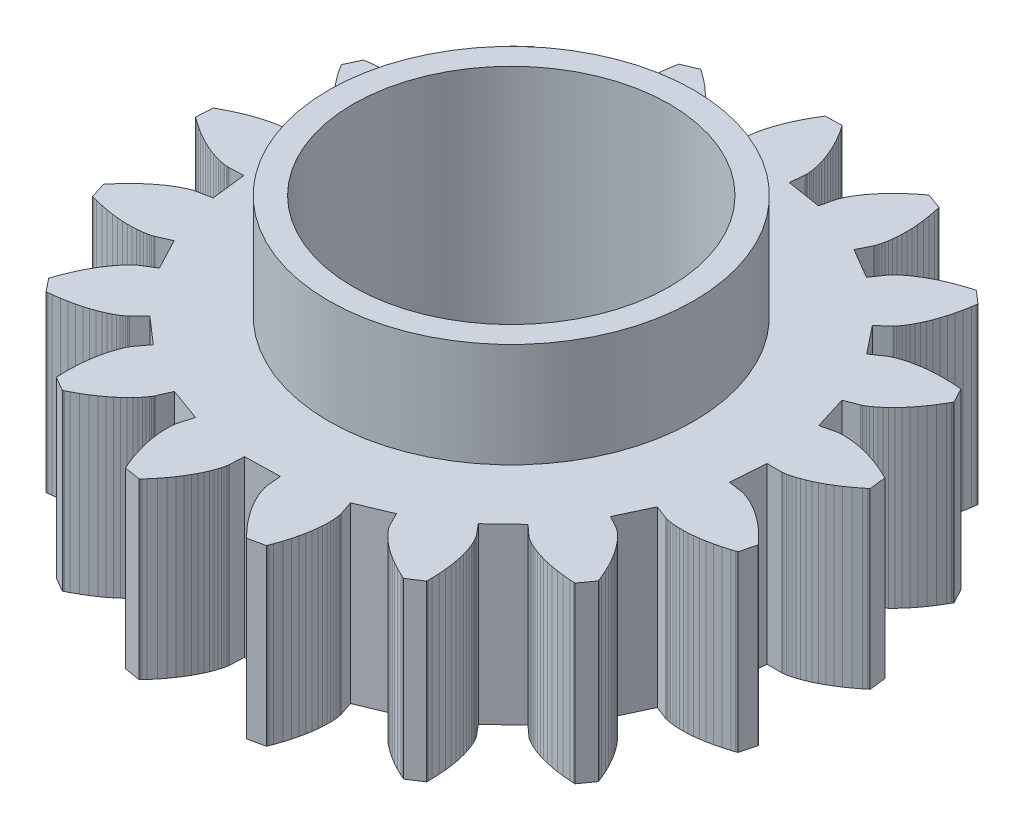
SolidWorks part; units mm, degrees
ref_plane "Front Plane" through (0, 0, 0) normal (0, 0, 1) x (1, 0, 0)
ref_plane "Top Plane" through (0, 0, 0) normal (0, 1, 0) x (1, 0, 0)
ref_plane "Right Plane" through (0, 0, 0) normal (1, 0, 0) x (0, 0, -1)
sketch "Sketch1" plane through (0, 0, 0) normal (0, 1, 0) x (1, 0, 0)
  line L0 (7.35, 0) -> (7.7663, 0)
  line L1 (7.7663, 0) -> (7.7784, 0.0005)
  line L2 (7.7784, 0.0005) -> (7.8035, 0.0026)
  line L3 (7.8035, 0.0026) -> (7.8416, 0.0072)
  line L4 (7.8416, 0.0072) -> (7.8923, 0.0155)
  line L5 (7.8923, 0.0155) -> (7.9555, 0.0285)
  line L6 (7.9555, 0.0285) -> (8.0307, 0.0472)
  line L7 (8.0307, 0.0472) -> (8.1178, 0.0727)
  line L8 (8.1178, 0.0727) -> (8.2161, 0.1059)
  line L9 (8.2161, 0.1059) -> (8.3252, 0.1478)
  line L10 (8.3252, 0.1478) -> (8.4445, 0.1994)
  line L11 (8.4445, 0.1994) -> (8.5734, 0.2615)
  line L12 (8.5734, 0.2615) -> (8.7111, 0.335)
  line L13 (8.7111, 0.335) -> (8.8571, 0.4207)
  line L14 (8.8571, 0.4207) -> (9.0104, 0.5194)
  line L15 (9.0104, 0.5194) -> (9.1702, 0.6319)
  line L16 (9.1702, 0.6319) -> (9.3357, 0.7588)
  line L17 (9.3357, 0.7588) -> (9.4203, 0.8278)
  line L18 (9.4203, 0.8278) -> (9.4416, 0.8457)
  line L19 (9.4416, 0.8457) -> (9.4523, 0.8547)
  line L20 (9.4523, 0.8547) -> (9.4576, 0.8593)
  line L21 (9.4576, 0.8593) -> (9.4603, 0.8615)
  line L22 (9.4603, 0.8615) -> (9.4606, 0.8618)
  line L23 (9.4606, 0.8618) -> (9.4608, 0.8621)
  line L24 (9.4608, 0.8621) -> (9.4055, 1.3364)
  line L25 (9.4055, 1.3364) -> (9.4053, 1.3367)
  line L26 (9.4053, 1.3367) -> (9.4049, 1.3369)
  line L27 (9.4049, 1.3369) -> (9.4018, 1.3385)
  line L28 (9.4018, 1.3385) -> (9.3955, 1.3416)
  line L29 (9.3955, 1.3416) -> (9.3831, 1.348)
  line L30 (9.3831, 1.348) -> (9.3582, 1.3605)
  line L31 (9.3582, 1.3605) -> (9.26, 1.4082)
  line L32 (9.26, 1.4082) -> (9.0698, 1.4937)
  line L33 (9.0698, 1.4937) -> (8.8884, 1.5664)
  line L34 (8.8884, 1.5664) -> (8.7165, 1.6272)
  line L35 (8.7165, 1.6272) -> (8.5547, 1.677)
  line L36 (8.5547, 1.677) -> (8.4038, 1.7169)
  line L37 (8.4038, 1.7169) -> (8.2641, 1.7477)
  line L38 (8.2641, 1.7477) -> (8.1361, 1.7704)
  line L39 (8.1361, 1.7704) -> (8.0203, 1.7861)
  line L40 (8.0203, 1.7861) -> (7.917, 1.7959)
  line L41 (7.917, 1.7959) -> (7.8264, 1.8007)
  line L42 (7.8264, 1.8007) -> (7.7488, 1.8016)
  line L43 (7.7488, 1.8016) -> (7.6844, 1.7997)
  line L44 (7.6844, 1.7997) -> (7.6331, 1.7961)
  line L45 (7.6331, 1.7961) -> (7.595, 1.7919)
  line L46 (7.595, 1.7919) -> (7.5701, 1.7881)
  line L47 (7.5701, 1.7881) -> (7.5582, 1.7858)
  line L48 (7.5582, 1.7858) -> (7.1531, 1.6901)
  line L49 (7.1531, 1.6901) -> (6.8537, 2.6551)
  line L50 (6.8537, 2.6551) -> (7.2419, 2.8055)
  line L51 (7.2419, 2.8055) -> (7.253, 2.8104)
  line L52 (7.253, 2.8104) -> (7.2757, 2.8213)
  line L53 (7.2757, 2.8213) -> (7.3094, 2.8394)
  line L54 (7.3094, 2.8394) -> (7.3537, 2.8655)
  line L55 (7.3537, 2.8655) -> (7.408, 2.9004)
  line L56 (7.408, 2.9004) -> (7.4714, 2.9451)
  line L57 (7.4714, 2.9451) -> (7.5433, 3.0003)
  line L58 (7.5433, 3.0003) -> (7.623, 3.0668)
  line L59 (7.623, 3.0668) -> (7.7096, 3.1453)
  line L60 (7.7096, 3.1453) -> (7.8022, 3.2364)
  line L61 (7.8022, 3.2364) -> (7.9, 3.3409)
  line L62 (7.9, 3.3409) -> (8.0019, 3.4592)
  line L63 (8.0019, 3.4592) -> (8.107, 3.5918)
  line L64 (8.107, 3.5918) -> (8.2143, 3.7393)
  line L65 (8.2143, 3.7393) -> (8.3227, 3.9019)
  line L66 (8.3227, 3.9019) -> (8.4312, 4.08)
  line L67 (8.4312, 4.08) -> (8.4851, 4.1749)
  line L68 (8.4851, 4.1749) -> (8.4985, 4.1993)
  line L69 (8.4985, 4.1993) -> (8.5052, 4.2116)
  line L70 (8.5052, 4.2116) -> (8.5085, 4.2177)
  line L71 (8.5085, 4.2177) -> (8.5102, 4.2208)
  line L72 (8.5102, 4.2208) -> (8.5104, 4.2212)
  line L73 (8.5104, 4.2212) -> (8.5105, 4.2215)
  line L74 (8.5105, 4.2215) -> (8.2876, 4.6439)
  line L75 (8.2876, 4.6439) -> (8.2873, 4.644)
  line L76 (8.2873, 4.644) -> (8.2869, 4.644)
  line L77 (8.2869, 4.644) -> (8.2834, 4.6444)
  line L78 (8.2834, 4.6444) -> (8.2764, 4.6451)
  line L79 (8.2764, 4.6451) -> (8.2625, 4.6465)
  line L80 (8.2625, 4.6465) -> (8.2348, 4.6492)
  line L81 (8.2348, 4.6492) -> (8.126, 4.6582)
  line L82 (8.126, 4.6582) -> (7.9178, 4.6692)
  line L83 (7.9178, 4.6692) -> (7.7223, 4.6714)
  line L84 (7.7223, 4.6714) -> (7.5401, 4.6661)
  line L85 (7.5401, 4.6661) -> (7.3712, 4.6541)
  line L86 (7.3712, 4.6541) -> (7.2161, 4.6367)
  line L87 (7.2161, 4.6367) -> (7.0747, 4.615)
  line L88 (7.0747, 4.615) -> (6.9471, 4.59)
  line L89 (6.9471, 4.59) -> (6.8335, 4.5628)
  line L90 (6.8335, 4.5628) -> (6.7336, 4.5345)
  line L91 (6.7336, 4.5345) -> (6.6474, 4.5063)
  line L92 (6.6474, 4.5063) -> (6.5748, 4.4791)
  line L93 (6.5748, 4.4791) -> (6.5153, 4.4541)
  line L94 (6.5153, 4.4541) -> (6.4688, 4.4322)
  line L95 (6.4688, 4.4322) -> (6.4349, 4.4145)
  line L96 (6.4349, 4.4145) -> (6.413, 4.402)
  line L97 (6.413, 4.402) -> (6.4027, 4.3955)
  line L98 (6.4027, 4.3955) -> (6.0595, 4.1599)
  line L99 (6.0595, 4.1599) -> (5.4317, 4.9517)
  line L100 (5.4317, 4.9517) -> (5.7394, 5.2321)
  line L101 (5.7394, 5.2321) -> (5.748, 5.2407)
  line L102 (5.748, 5.2407) -> (5.7652, 5.2591)
  line L103 (5.7652, 5.2591) -> (5.7901, 5.2881)
  line L104 (5.7901, 5.2881) -> (5.822, 5.3284)
  line L105 (5.822, 5.3284) -> (5.86, 5.3806)
  line L106 (5.86, 5.3806) -> (5.903, 5.4452)
  line L107 (5.903, 5.4452) -> (5.9501, 5.5226)
  line L108 (5.9501, 5.5226) -> (6.0004, 5.6134)
  line L109 (6.0004, 5.6134) -> (6.0528, 5.7179)
  line L110 (6.0528, 5.7179) -> (6.1062, 5.8364)
  line L111 (6.1062, 5.8364) -> (6.1596, 5.9691)
  line L112 (6.1596, 5.9691) -> (6.2119, 6.1162)
  line L113 (6.2119, 6.1162) -> (6.262, 6.2779)
  line L114 (6.262, 6.2779) -> (6.3088, 6.4541)
  line L115 (6.3088, 6.4541) -> (6.3512, 6.6449)
  line L116 (6.3512, 6.6449) -> (6.388, 6.8502)
  line L117 (6.388, 6.8502) -> (6.4039, 6.9582)
  line L118 (6.4039, 6.9582) -> (6.4077, 6.9857)
  line L119 (6.4077, 6.9857) -> (6.4095, 6.9996)
  line L120 (6.4095, 6.9996) -> (6.4104, 7.0066)
  line L121 (6.4104, 7.0066) -> (6.4108, 7.01)
  line L122 (6.4108, 7.01) -> (6.4109, 7.0105)
  line L123 (6.4109, 7.0105) -> (6.4108, 7.0108)
  line L124 (6.4108, 7.0108) -> (6.0504, 7.3241)
  line L125 (6.0504, 7.3241) -> (6.0501, 7.3241)
  line L126 (6.0501, 7.3241) -> (6.0497, 7.324)
  line L127 (6.0497, 7.324) -> (6.0463, 7.3231)
  line L128 (6.0463, 7.3231) -> (6.0395, 7.3212)
  line L129 (6.0395, 7.3212) -> (6.026, 7.3175)
  line L130 (6.026, 7.3175) -> (5.9993, 7.31)
  line L131 (5.9993, 7.31) -> (5.8945, 7.2791)
  line L132 (5.8945, 7.2791) -> (5.6964, 7.2141)
  line L133 (5.6964, 7.2141) -> (5.5133, 7.1456)
  line L134 (5.5133, 7.1456) -> (5.3453, 7.0748)
  line L135 (5.3453, 7.0748) -> (5.1922, 7.0026)
  line L136 (5.1922, 7.0026) -> (5.0538, 6.9304)
  line L137 (5.0538, 6.9304) -> (4.9298, 6.859)
  line L138 (4.9298, 6.859) -> (4.8199, 6.7896)
  line L139 (4.8199, 6.7896) -> (4.7237, 6.7232)
  line L140 (4.7237, 6.7232) -> (4.6408, 6.6608)
  line L141 (4.6408, 6.6608) -> (4.5707, 6.6033)
  line L142 (4.5707, 6.6033) -> (4.5127, 6.5517)
  line L143 (4.5127, 6.5517) -> (4.4664, 6.5069)
  line L144 (4.4664, 6.5069) -> (4.4309, 6.4697)
  line L145 (4.4309, 6.4697) -> (4.4056, 6.441)
  line L146 (4.4056, 6.441) -> (4.3898, 6.4214)
  line L147 (4.3898, 6.4214) -> (4.3825, 6.4117)
  line L148 (4.3825, 6.4117) -> (4.1476, 6.068)
  line L149 (4.1476, 6.068) -> (3.2762, 6.5794)
  line L150 (3.2762, 6.5794) -> (3.4617, 6.9521)
  line L151 (3.4617, 6.9521) -> (3.4667, 6.9632)
  line L152 (3.4667, 6.9632) -> (3.4761, 6.9866)
  line L153 (3.4761, 6.9866) -> (3.4889, 7.0227)
  line L154 (3.4889, 7.0227) -> (3.504, 7.0718)
  line L155 (3.504, 7.0718) -> (3.5206, 7.1341)
  line L156 (3.5206, 7.1341) -> (3.5373, 7.2099)
  line L157 (3.5373, 7.2099) -> (3.5533, 7.2991)
  line L158 (3.5533, 7.2991) -> (3.5674, 7.402)
  line L159 (3.5674, 7.402) -> (3.5785, 7.5183)
  line L160 (3.5785, 7.5183) -> (3.5855, 7.6481)
  line L161 (3.5855, 7.6481) -> (3.5874, 7.7911)
  line L162 (3.5874, 7.7911) -> (3.583, 7.9472)
  line L163 (3.583, 7.9472) -> (3.5713, 8.1161)
  line L164 (3.5713, 8.1161) -> (3.5513, 8.2973)
  line L165 (3.5513, 8.2973) -> (3.5219, 8.4905)
  line L166 (3.5219, 8.4905) -> (3.482, 8.6952)
  line L167 (3.482, 8.6952) -> (3.4579, 8.8017)
  line L168 (3.4579, 8.8017) -> (3.4514, 8.8287)
  line L169 (3.4514, 8.8287) -> (3.4481, 8.8423)
  line L170 (3.4481, 8.8423) -> (3.4464, 8.8491)
  line L171 (3.4464, 8.8491) -> (3.4456, 8.8525)
  line L172 (3.4456, 8.8525) -> (3.4455, 8.8529)
  line L173 (3.4455, 8.8529) -> (3.4453, 8.8532)
  line L174 (3.4453, 8.8532) -> (2.9961, 9.0152)
  line L175 (2.9961, 9.0152) -> (2.9958, 9.0151)
  line L176 (2.9958, 9.0151) -> (2.9954, 9.0148)
  line L177 (2.9954, 9.0148) -> (2.9926, 9.0127)
  line L178 (2.9926, 9.0127) -> (2.987, 9.0085)
  line L179 (2.987, 9.0085) -> (2.9757, 9.0002)
  line L180 (2.9757, 9.0002) -> (2.9535, 8.9835)
  line L181 (2.9535, 8.9835) -> (2.867, 8.9169)
  line L182 (2.867, 8.9169) -> (2.7057, 8.7847)
  line L183 (2.7057, 8.7847) -> (2.5597, 8.6547)
  line L184 (2.5597, 8.6547) -> (2.4287, 8.528)
  line L185 (2.4287, 8.528) -> (2.3119, 8.4054)
  line L186 (2.3119, 8.4054) -> (2.209, 8.288)
  line L187 (2.209, 8.288) -> (2.1191, 8.1767)
  line L188 (2.1191, 8.1767) -> (2.0417, 8.0723)
  line L189 (2.0417, 8.0723) -> (1.9761, 7.9756)
  line L190 (1.9761, 7.9756) -> (1.9213, 7.8875)
  line L191 (1.9213, 7.8875) -> (1.8766, 7.8085)
  line L192 (1.8766, 7.8085) -> (1.8412, 7.7395)
  line L193 (1.8412, 7.7395) -> (1.8142, 7.681)
  line L194 (1.8142, 7.681) -> (1.7946, 7.6335)
  line L195 (1.7946, 7.6335) -> (1.7814, 7.5975)
  line L196 (1.7814, 7.5975) -> (1.7737, 7.5735)
  line L197 (1.7737, 7.5735) -> (1.7704, 7.5618)
  line L198 (1.7704, 7.5618) -> (1.6755, 7.1565)
  line L199 (1.6755, 7.1565) -> (0.6782, 7.3186)
  line L200 (0.6782, 7.3186) -> (0.7166, 7.7332)
  line L201 (0.7166, 7.7332) -> (0.7172, 7.7453)
  line L202 (0.7172, 7.7453) -> (0.7175, 7.7705)
  line L203 (0.7175, 7.7705) -> (0.7164, 7.8088)
  line L204 (0.7164, 7.8088) -> (0.7128, 7.8601)
  line L205 (0.7128, 7.8601) -> (0.7057, 7.9241)
  line L206 (0.7057, 7.9241) -> (0.694, 8.0008)
  line L207 (0.694, 8.0008) -> (0.6766, 8.0899)
  line L208 (0.6766, 8.0899) -> (0.6526, 8.1908)
  line L209 (0.6526, 8.1908) -> (0.6209, 8.3033)
  line L210 (0.6209, 8.3033) -> (0.5806, 8.4269)
  line L211 (0.5806, 8.4269) -> (0.5307, 8.5609)
  line L212 (0.5307, 8.5609) -> (0.4702, 8.7049)
  line L213 (0.4702, 8.7049) -> (0.3983, 8.8581)
  line L214 (0.3983, 8.8581) -> (0.3142, 9.0199)
  line L215 (0.3142, 9.0199) -> (0.2169, 9.1894)
  line L216 (0.2169, 9.1894) -> (0.1058, 9.3659)
  line L217 (0.1058, 9.3659) -> (0.0449, 9.4565)
  line L218 (0.0449, 9.4565) -> (0.0291, 9.4793)
  line L219 (0.0291, 9.4793) -> (0.0211, 9.4908)
  line L220 (0.0211, 9.4908) -> (0.017, 9.4965)
  line L221 (0.017, 9.4965) -> (0.015, 9.4994)
  line L222 (0.015, 9.4994) -> (0.0148, 9.4998)
  line L223 (0.0148, 9.4998) -> (0.0145, 9.5)
  line L224 (0.0145, 9.5) -> (-0.4629, 9.4887)
  line L225 (-0.4629, 9.4887) -> (-0.4632, 9.4885)
  line L226 (-0.4632, 9.4885) -> (-0.4634, 9.4881)
  line L227 (-0.4634, 9.4881) -> (-0.4653, 9.4852)
  line L228 (-0.4653, 9.4852) -> (-0.469, 9.4792)
  line L229 (-0.469, 9.4792) -> (-0.4765, 9.4674)
  line L230 (-0.4765, 9.4674) -> (-0.4912, 9.4438)
  line L231 (-0.4912, 9.4438) -> (-0.5478, 9.3505)
  line L232 (-0.5478, 9.3505) -> (-0.6504, 9.1689)
  line L233 (-0.6504, 9.1689) -> (-0.7396, 8.995)
  line L234 (-0.7396, 8.995) -> (-0.816, 8.8294)
  line L235 (-0.816, 8.8294) -> (-0.8806, 8.673)
  line L236 (-0.8806, 8.673) -> (-0.9342, 8.5263)
  line L237 (-0.9342, 8.5263) -> (-0.9777, 8.3901)
  line L238 (-0.9777, 8.3901) -> (-1.0122, 8.2647)
  line L239 (-1.0122, 8.2647) -> (-1.0385, 8.1509)
  line L240 (-1.0385, 8.1509) -> (-1.0577, 8.0489)
  line L241 (-1.0577, 8.0489) -> (-1.0708, 7.9592)
  line L242 (-1.0708, 7.9592) -> (-1.0789, 7.882)
  line L243 (-1.0789, 7.882) -> (-1.083, 7.8176)
  line L244 (-1.083, 7.8176) -> (-1.0842, 7.7663)
  line L245 (-1.0842, 7.7663) -> (-1.0835, 7.728)
  line L246 (-1.0835, 7.728) -> (-1.082, 7.7028)
  line L247 (-1.082, 7.7028) -> (-1.0808, 7.6907)
  line L248 (-1.0808, 7.6907) -> (-1.0229, 7.2785)
  line L249 (-1.0229, 7.2785) -> (-2.0114, 7.0694)
  line L250 (-2.0114, 7.0694) -> (-2.1254, 7.4698)
  line L251 (-2.1254, 7.4698) -> (-2.1292, 7.4813)
  line L252 (-2.1292, 7.4813) -> (-2.138, 7.505)
  line L253 (-2.138, 7.505) -> (-2.1529, 7.5403)
  line L254 (-2.1529, 7.5403) -> (-2.1747, 7.5868)
  line L255 (-2.1747, 7.5868) -> (-2.2045, 7.644)
  line L256 (-2.2045, 7.644) -> (-2.2431, 7.7113)
  line L257 (-2.2431, 7.7113) -> (-2.2915, 7.788)
  line L258 (-2.2915, 7.788) -> (-2.3503, 7.8735)
  line L259 (-2.3503, 7.8735) -> (-2.4205, 7.9669)
  line L260 (-2.4205, 7.9669) -> (-2.5027, 8.0675)
  line L261 (-2.5027, 8.0675) -> (-2.5977, 8.1745)
  line L262 (-2.5977, 8.1745) -> (-2.7061, 8.2869)
  line L263 (-2.7061, 8.2869) -> (-2.8285, 8.4038)
  line L264 (-2.8285, 8.4038) -> (-2.9654, 8.5243)
  line L265 (-2.9654, 8.5243) -> (-3.1173, 8.6472)
  line L266 (-3.1173, 8.6472) -> (-3.2847, 8.7717)
  line L267 (-3.2847, 8.7717) -> (-3.3742, 8.8341)
  line L268 (-3.3742, 8.8341) -> (-3.3972, 8.8497)
  line L269 (-3.3972, 8.8497) -> (-3.4088, 8.8575)
  line L270 (-3.4088, 8.8575) -> (-3.4147, 8.8614)
  line L271 (-3.4147, 8.8614) -> (-3.4176, 8.8634)
  line L272 (-3.4176, 8.8634) -> (-3.4179, 8.8636)
  line L273 (-3.4179, 8.8636) -> (-3.4183, 8.8637)
  line L274 (-3.4183, 8.8637) -> (-3.8594, 8.6807)
  line L275 (-3.8594, 8.6807) -> (-3.8595, 8.6804)
  line L276 (-3.8595, 8.6804) -> (-3.8596, 8.68)
  line L277 (-3.8596, 8.68) -> (-3.8603, 8.6766)
  line L278 (-3.8603, 8.6766) -> (-3.8616, 8.6697)
  line L279 (-3.8616, 8.6697) -> (-3.8643, 8.656)
  line L280 (-3.8643, 8.656) -> (-3.8695, 8.6287)
  line L281 (-3.8695, 8.6287) -> (-3.8886, 8.5212)
  line L282 (-3.8886, 8.5212) -> (-3.9187, 8.3148)
  line L283 (-3.9187, 8.3148) -> (-3.939, 8.1204)
  line L284 (-3.939, 8.1204) -> (-3.9505, 7.9384)
  line L285 (-3.9505, 7.9384) -> (-3.9541, 7.7692)
  line L286 (-3.9541, 7.7692) -> (-3.9511, 7.6131)
  line L287 (-3.9511, 7.6131) -> (-3.9425, 7.4703)
  line L288 (-3.9425, 7.4703) -> (-3.9294, 7.341)
  line L289 (-3.9294, 7.341) -> (-3.9128, 7.2253)
  line L290 (-3.9128, 7.2253) -> (-3.8939, 7.1233)
  line L291 (-3.8939, 7.1233) -> (-3.8737, 7.0349)
  line L292 (-3.8737, 7.0349) -> (-3.8534, 6.96)
  line L293 (-3.8534, 6.96) -> (-3.8339, 6.8985)
  line L294 (-3.8339, 6.8985) -> (-3.8164, 6.8502)
  line L295 (-3.8164, 6.8502) -> (-3.802, 6.8147)
  line L296 (-3.802, 6.8147) -> (-3.7915, 6.7918)
  line L297 (-3.7915, 6.7918) -> (-3.786, 6.781)
  line L298 (-3.786, 6.781) -> (-3.5831, 6.4175)
  line L299 (-3.5831, 6.4175) -> (-4.4294, 5.8654)
  line L300 (-4.4294, 5.8654) -> (-4.6803, 6.1976)
  line L301 (-4.6803, 6.1976) -> (-4.688, 6.207)
  line L302 (-4.688, 6.207) -> (-4.7047, 6.2258)
  line L303 (-4.7047, 6.2258) -> (-4.7313, 6.2534)
  line L304 (-4.7313, 6.2534) -> (-4.7685, 6.2889)
  line L305 (-4.7685, 6.2889) -> (-4.817, 6.3314)
  line L306 (-4.817, 6.3314) -> (-4.8773, 6.3802)
  line L307 (-4.8773, 6.3802) -> (-4.9501, 6.4343)
  line L308 (-4.9501, 6.4343) -> (-5.0358, 6.4927)
  line L309 (-5.0358, 6.4927) -> (-5.135, 6.5545)
  line L310 (-5.135, 6.5545) -> (-5.2481, 6.6187)
  line L311 (-5.2481, 6.6187) -> (-5.3753, 6.6841)
  line L312 (-5.3753, 6.6841) -> (-5.517, 6.7498)
  line L313 (-5.517, 6.7498) -> (-5.6733, 6.8146)
  line L314 (-5.6733, 6.8146) -> (-5.8445, 6.8774)
  line L315 (-5.8445, 6.8774) -> (-6.0306, 6.9372)
  line L316 (-6.0306, 6.9372) -> (-6.2315, 6.9928)
  line L317 (-6.2315, 6.9928) -> (-6.3376, 7.0186)
  line L318 (-6.3376, 7.0186) -> (-6.3647, 7.0249)
  line L319 (-6.3647, 7.0249) -> (-6.3784, 7.028)
  line L320 (-6.3784, 7.028) -> (-6.3852, 7.0295)
  line L321 (-6.3852, 7.0295) -> (-6.3886, 7.0303)
  line L322 (-6.3886, 7.0303) -> (-6.389, 7.0304)
  line L323 (-6.389, 7.0304) -> (-6.3894, 7.0304)
  line L324 (-6.3894, 7.0304) -> (-6.7346, 6.7004)
  line L325 (-6.7346, 6.7004) -> (-6.7346, 6.7001)
  line L326 (-6.7346, 6.7001) -> (-6.7346, 6.6996)
  line L327 (-6.7346, 6.6996) -> (-6.7339, 6.6962)
  line L328 (-6.7339, 6.6962) -> (-6.7327, 6.6893)
  line L329 (-6.7327, 6.6893) -> (-6.7303, 6.6755)
  line L330 (-6.7303, 6.6755) -> (-6.7252, 6.6482)
  line L331 (-6.7252, 6.6482) -> (-6.7042, 6.541)
  line L332 (-6.7042, 6.541) -> (-6.6577, 6.3377)
  line L333 (-6.6577, 6.3377) -> (-6.6064, 6.1491)
  line L334 (-6.6064, 6.1491) -> (-6.5514, 5.9753)
  line L335 (-6.5514, 5.9753) -> (-6.4937, 5.8162)
  line L336 (-6.4937, 5.8162) -> (-6.4345, 5.6717)
  line L337 (-6.4345, 5.6717) -> (-6.3749, 5.5416)
  line L338 (-6.3749, 5.5416) -> (-6.3159, 5.4258)
  line L339 (-6.3159, 5.4258) -> (-6.2587, 5.3239)
  line L340 (-6.2587, 5.3239) -> (-6.2042, 5.2356)
  line L341 (-6.2042, 5.2356) -> (-6.1534, 5.1605)
  line L342 (-6.1534, 5.1605) -> (-6.1074, 5.098)
  line L343 (-6.1074, 5.098) -> (-6.0671, 5.0477)
  line L344 (-6.0671, 5.0477) -> (-6.0333, 5.0089)
  line L345 (-6.0333, 5.0089) -> (-6.007, 4.9811)
  line L346 (-6.007, 4.9811) -> (-5.9889, 4.9635)
  line L347 (-5.9889, 4.9635) -> (-5.9799, 4.9554)
  line L348 (-5.9799, 4.9554) -> (-5.6594, 4.6898)
  line L349 (-5.6594, 4.6898) -> (-6.2491, 3.8693)
  line L350 (-6.2491, 3.8693) -> (-6.6031, 4.0884)
  line L351 (-6.6031, 4.0884) -> (-6.6136, 4.0944)
  line L352 (-6.6136, 4.0944) -> (-6.6361, 4.1059)
  line L353 (-6.6361, 4.1059) -> (-6.6708, 4.1219)
  line L354 (-6.6708, 4.1219) -> (-6.7183, 4.1416)
  line L355 (-6.7183, 4.1416) -> (-6.7789, 4.1638)
  line L356 (-6.7789, 4.1638) -> (-6.8527, 4.1875)
  line L357 (-6.8527, 4.1875) -> (-6.9401, 4.2116)
  line L358 (-6.9401, 4.2116) -> (-7.0412, 4.2352)
  line L359 (-7.0412, 4.2352) -> (-7.156, 4.2569)
  line L360 (-7.156, 4.2569) -> (-7.2846, 4.2759)
  line L361 (-7.2846, 4.2759) -> (-7.4269, 4.291)
  line L362 (-7.4269, 4.291) -> (-7.5827, 4.301)
  line L363 (-7.5827, 4.301) -> (-7.7519, 4.305)
  line L364 (-7.7519, 4.305) -> (-7.9342, 4.3017)
  line L365 (-7.9342, 4.3017) -> (-8.1293, 4.2903)
  line L366 (-8.1293, 4.2903) -> (-8.3368, 4.2695)
  line L367 (-8.3368, 4.2695) -> (-8.4451, 4.2553)
  line L368 (-8.4451, 4.2553) -> (-8.4726, 4.2513)
  line L369 (-8.4726, 4.2513) -> (-8.4864, 4.2493)
  line L370 (-8.4864, 4.2493) -> (-8.4934, 4.2482)
  line L371 (-8.4934, 4.2482) -> (-8.4968, 4.2477)
  line L372 (-8.4968, 4.2477) -> (-8.4973, 4.2476)
  line L373 (-8.4973, 4.2476) -> (-8.4976, 4.2475)
  line L374 (-8.4976, 4.2475) -> (-8.7003, 3.8151)
  line L375 (-8.7003, 3.8151) -> (-8.7002, 3.8148)
  line L376 (-8.7002, 3.8148) -> (-8.7, 3.8144)
  line L377 (-8.7, 3.8144) -> (-8.6982, 3.8114)
  line L378 (-8.6982, 3.8114) -> (-8.6945, 3.8054)
  line L379 (-8.6945, 3.8054) -> (-8.6872, 3.7935)
  line L380 (-8.6872, 3.7935) -> (-8.6727, 3.7698)
  line L381 (-8.6727, 3.7698) -> (-8.6144, 3.6775)
  line L382 (-8.6144, 3.6775) -> (-8.4976, 3.5047)
  line L383 (-8.4976, 3.5047) -> (-8.3816, 3.3474)
  line L384 (-8.3816, 3.3474) -> (-8.2675, 3.2052)
  line L385 (-8.2675, 3.2052) -> (-8.1562, 3.0776)
  line L386 (-8.1562, 3.0776) -> (-8.0488, 2.9643)
  line L387 (-8.0488, 2.9643) -> (-7.9463, 2.8646)
  line L388 (-7.9463, 2.8646) -> (-7.8495, 2.7779)
  line L389 (-7.8495, 2.7779) -> (-7.7593, 2.7035)
  line L390 (-7.7593, 2.7035) -> (-7.6765, 2.6409)
  line L391 (-7.6765, 2.6409) -> (-7.6021, 2.5891)
  line L392 (-7.6021, 2.5891) -> (-7.5366, 2.5475)
  line L393 (-7.5366, 2.5475) -> (-7.4808, 2.5152)
  line L394 (-7.4808, 2.5152) -> (-7.4353, 2.4912)
  line L395 (-7.4353, 2.4912) -> (-7.4007, 2.4748)
  line L396 (-7.4007, 2.4748) -> (-7.3775, 2.4649)
  line L397 (-7.3775, 2.4649) -> (-7.3662, 2.4606)
  line L398 (-7.3662, 2.4606) -> (-6.9714, 2.3287)
  line L399 (-6.9714, 2.3287) -> (-7.2249, 1.3506)
  line L400 (-7.2249, 1.3506) -> (-7.6341, 1.427)
  line L401 (-7.6341, 1.427) -> (-7.6461, 1.4288)
  line L402 (-7.6461, 1.4288) -> (-7.6711, 1.4314)
  line L403 (-7.6711, 1.4314) -> (-7.7094, 1.4338)
  line L404 (-7.7094, 1.4338) -> (-7.7608, 1.435)
  line L405 (-7.7608, 1.435) -> (-7.8252, 1.4338)
  line L406 (-7.8252, 1.4338) -> (-7.9027, 1.4292)
  line L407 (-7.9027, 1.4292) -> (-7.9929, 1.4202)
  line L408 (-7.9929, 1.4202) -> (-8.0957, 1.4056)
  line L409 (-8.0957, 1.4056) -> (-8.2106, 1.3844)
  line L410 (-8.2106, 1.3844) -> (-8.3373, 1.3557)
  line L411 (-8.3373, 1.3557) -> (-8.4754, 1.3183)
  line L412 (-8.4754, 1.3183) -> (-8.6244, 1.2714)
  line L413 (-8.6244, 1.2714) -> (-8.7836, 1.2139)
  line L414 (-8.7836, 1.2139) -> (-8.9524, 1.1451)
  line L415 (-8.9524, 1.1451) -> (-9.1302, 1.0639)
  line L416 (-9.1302, 1.0639) -> (-9.3162, 0.9696)
  line L417 (-9.3162, 0.9696) -> (-9.412, 0.9172)
  line L418 (-9.412, 0.9172) -> (-9.4362, 0.9036)
  line L419 (-9.4362, 0.9036) -> (-9.4484, 0.8967)
  line L420 (-9.4484, 0.8967) -> (-9.4545, 0.8932)
  line L421 (-9.4545, 0.8932) -> (-9.4575, 0.8914)
  line L422 (-9.4575, 0.8914) -> (-9.4579, 0.8912)
  line L423 (-9.4579, 0.8912) -> (-9.4581, 0.891)
  line L424 (-9.4581, 0.891) -> (-9.4909, 0.4146)
  line L425 (-9.4909, 0.4146) -> (-9.4907, 0.4143)
  line L426 (-9.4907, 0.4143) -> (-9.4904, 0.414)
  line L427 (-9.4904, 0.414) -> (-9.4876, 0.4119)
  line L428 (-9.4876, 0.4119) -> (-9.4821, 0.4076)
  line L429 (-9.4821, 0.4076) -> (-9.471, 0.3991)
  line L430 (-9.471, 0.3991) -> (-9.4488, 0.3823)
  line L431 (-9.4488, 0.3823) -> (-9.3611, 0.3173)
  line L432 (-9.3611, 0.3173) -> (-9.1898, 0.1983)
  line L433 (-9.1898, 0.1983) -> (-9.0249, 0.0935)
  line L434 (-9.0249, 0.0935) -> (-8.8671, 0.0022)
  line L435 (-8.8671, 0.0022) -> (-8.7172, -0.0766)
  line L436 (-8.7172, -0.0766) -> (-8.5761, -0.1435)
  line L437 (-8.5761, -0.1435) -> (-8.4445, -0.1994)
  line L438 (-8.4445, -0.1994) -> (-8.3229, -0.2453)
  line L439 (-8.3229, -0.2453) -> (-8.2119, -0.282)
  line L440 (-8.2119, -0.282) -> (-8.1122, -0.3106)
  line L441 (-8.1122, -0.3106) -> (-8.024, -0.3319)
  line L442 (-8.024, -0.3319) -> (-7.9479, -0.3471)
  line L443 (-7.9479, -0.3471) -> (-7.8842, -0.3571)
  line L444 (-7.8842, -0.3571) -> (-7.8332, -0.363)
  line L445 (-7.8332, -0.363) -> (-7.795, -0.3658)
  line L446 (-7.795, -0.3658) -> (-7.7698, -0.3666)
  line L447 (-7.7698, -0.3666) -> (-7.7577, -0.3666)
  line L448 (-7.7577, -0.3666) -> (-7.3418, -0.3469)
  line L449 (-7.3418, -0.3469) -> (-7.2249, -1.3506)
  line L450 (-7.2249, -1.3506) -> (-7.6341, -1.4271)
  line L451 (-7.6341, -1.4271) -> (-7.6459, -1.4298)
  line L452 (-7.6459, -1.4298) -> (-7.6702, -1.4364)
  line L453 (-7.6702, -1.4364) -> (-7.7067, -1.448)
  line L454 (-7.7067, -1.448) -> (-7.7551, -1.4654)
  line L455 (-7.7551, -1.4654) -> (-7.8148, -1.4898)
  line L456 (-7.8148, -1.4898) -> (-7.8853, -1.5221)
  line L457 (-7.8853, -1.5221) -> (-7.9662, -1.5631)
  line L458 (-7.9662, -1.5631) -> (-8.0567, -1.6138)
  line L459 (-8.0567, -1.6138) -> (-8.1563, -1.6751)
  line L460 (-8.1563, -1.6751) -> (-8.2641, -1.7477)
  line L461 (-8.2641, -1.7477) -> (-8.3793, -1.8324)
  line L462 (-8.3793, -1.8324) -> (-8.5013, -1.93)
  line L463 (-8.5013, -1.93) -> (-8.629, -2.041)
  line L464 (-8.629, -2.041) -> (-8.7615, -2.1662)
  line L465 (-8.7615, -2.1662) -> (-8.898, -2.3062)
  line L466 (-8.898, -2.3062) -> (-9.0373, -2.4613)
  line L467 (-9.0373, -2.4613) -> (-9.1078, -2.5447)
  line L468 (-9.1078, -2.5447) -> (-9.1254, -2.5662)
  line L469 (-9.1254, -2.5662) -> (-9.1343, -2.577)
  line L470 (-9.1343, -2.577) -> (-9.1387, -2.5825)
  line L471 (-9.1387, -2.5825) -> (-9.1409, -2.5852)
  line L472 (-9.1409, -2.5852) -> (-9.1412, -2.5855)
  line L473 (-9.1412, -2.5855) -> (-9.1413, -2.5858)
  line L474 (-9.1413, -2.5858) -> (-8.9998, -3.0419)
  line L475 (-8.9998, -3.0419) -> (-8.9995, -3.0421)
  line L476 (-8.9995, -3.0421) -> (-8.9991, -3.0422)
  line L477 (-8.9991, -3.0422) -> (-8.9957, -3.0432)
  line L478 (-8.9957, -3.0432) -> (-8.989, -3.0452)
  line L479 (-8.989, -3.0452) -> (-8.9756, -3.0491)
  line L480 (-8.9756, -3.0491) -> (-8.9489, -3.0569)
  line L481 (-8.9489, -3.0569) -> (-8.8436, -3.0858)
  line L482 (-8.8436, -3.0858) -> (-8.6409, -3.1348)
  line L483 (-8.6409, -3.1348) -> (-8.4492, -3.1729)
  line L484 (-8.4492, -3.1729) -> (-8.2691, -3.2011)
  line L485 (-8.2691, -3.2011) -> (-8.1009, -3.2204)
  line L486 (-8.1009, -3.2204) -> (-7.9452, -3.2318)
  line L487 (-7.9452, -3.2318) -> (-7.8022, -3.2364)
  line L488 (-7.8022, -3.2364) -> (-7.6722, -3.2353)
  line L489 (-7.6722, -3.2353) -> (-7.5555, -3.2295)
  line L490 (-7.5555, -3.2295) -> (-7.4522, -3.22)
  line L491 (-7.4522, -3.22) -> (-7.3623, -3.2081)
  line L492 (-7.3623, -3.2081) -> (-7.2859, -3.1947)
  line L493 (-7.2859, -3.1947) -> (-7.2228, -3.1811)
  line L494 (-7.2228, -3.1811) -> (-7.1731, -3.1681)
  line L495 (-7.1731, -3.1681) -> (-7.1365, -3.157)
  line L496 (-7.1365, -3.157) -> (-7.1127, -3.1486)
  line L497 (-7.1127, -3.1486) -> (-7.1014, -3.1442)
  line L498 (-7.1014, -3.1442) -> (-6.7207, -2.9757)
  line L499 (-6.7207, -2.9757) -> (-6.2491, -3.8693)
  line L500 (-6.2491, -3.8693) -> (-6.603, -4.0885)
  line L501 (-6.603, -4.0885) -> (-6.6131, -4.0953)
  line L502 (-6.6131, -4.0953) -> (-6.6334, -4.1102)
  line L503 (-6.6334, -4.1102) -> (-6.6632, -4.1342)
  line L504 (-6.6632, -4.1342) -> (-6.702, -4.1679)
  line L505 (-6.702, -4.1679) -> (-6.7489, -4.2122)
  line L506 (-6.7489, -4.2122) -> (-6.803, -4.2678)
  line L507 (-6.803, -4.2678) -> (-6.8636, -4.3353)
  line L508 (-6.8636, -4.3353) -> (-6.9297, -4.4153)
  line L509 (-6.9297, -4.4153) -> (-7.0004, -4.5083)
  line L510 (-7.0004, -4.5083) -> (-7.0747, -4.615)
  line L511 (-7.0747, -4.615) -> (-7.1516, -4.7356)
  line L512 (-7.1516, -4.7356) -> (-7.23, -4.8706)
  line L513 (-7.23, -4.8706) -> (-7.309, -5.0203)
  line L514 (-7.309, -5.0203) -> (-7.3873, -5.185)
  line L515 (-7.3873, -5.185) -> (-7.464, -5.3647)
  line L516 (-7.464, -5.3647) -> (-7.5379, -5.5597)
  line L517 (-7.5379, -5.5597) -> (-7.5735, -5.663)
  line L518 (-7.5735, -5.663) -> (-7.5822, -5.6894)
  line L519 (-7.5822, -5.6894) -> (-7.5865, -5.7027)
  line L520 (-7.5865, -5.7027) -> (-7.5887, -5.7094)
  line L521 (-7.5887, -5.7094) -> (-7.5897, -5.7127)
  line L522 (-7.5897, -5.7127) -> (-7.5899, -5.7131)
  line L523 (-7.5899, -5.7131) -> (-7.5899, -5.7134)
  line L524 (-7.5899, -5.7134) -> (-7.2932, -6.0876)
  line L525 (-7.2932, -6.0876) -> (-7.2929, -6.0877)
  line L526 (-7.2929, -6.0877) -> (-7.2924, -6.0877)
  line L527 (-7.2924, -6.0877) -> (-7.2889, -6.0874)
  line L528 (-7.2889, -6.0874) -> (-7.2819, -6.0868)
  line L529 (-7.2819, -6.0868) -> (-7.268, -6.0856)
  line L530 (-7.268, -6.0856) -> (-7.2403, -6.0831)
  line L531 (-7.2403, -6.0831) -> (-7.1317, -6.0721)
  line L532 (-7.1317, -6.0721) -> (-6.925, -6.0446)
  line L533 (-6.925, -6.0446) -> (-6.7325, -6.0109)
  line L534 (-6.7325, -6.0109) -> (-6.5543, -5.9721)
  line L535 (-6.5543, -5.9721) -> (-6.3905, -5.9293)
  line L536 (-6.3905, -5.9293) -> (-6.2412, -5.8837)
  line L537 (-6.2412, -5.8837) -> (-6.1062, -5.8364)
  line L538 (-6.1062, -5.8364) -> (-5.9854, -5.7883)
  line L539 (-5.9854, -5.7883) -> (-5.8787, -5.7407)
  line L540 (-5.8787, -5.7407) -> (-5.7857, -5.6946)
  line L541 (-5.7857, -5.6946) -> (-5.7062, -5.651)
  line L542 (-5.7062, -5.651) -> (-5.6398, -5.611)
  line L543 (-5.6398, -5.611) -> (-5.586, -5.5754)
  line L544 (-5.586, -5.5754) -> (-5.5443, -5.5454)
  line L545 (-5.5443, -5.5454) -> (-5.5141, -5.5218)
  line L546 (-5.5141, -5.5218) -> (-5.4949, -5.5054)
  line L547 (-5.4949, -5.5054) -> (-5.486, -5.4972)
  line L548 (-5.486, -5.4972) -> (-5.1919, -5.2025)
  line L549 (-5.1919, -5.2025) -> (-4.4294, -5.8654)
  line L550 (-4.4294, -5.8654) -> (-4.6802, -6.1977)
  line L551 (-4.6802, -6.1977) -> (-4.6871, -6.2076)
  line L552 (-4.6871, -6.2076) -> (-4.7006, -6.2289)
  line L553 (-4.7006, -6.2289) -> (-4.7199, -6.262)
  line L554 (-4.7199, -6.262) -> (-4.7438, -6.3075)
  line L555 (-4.7438, -6.3075) -> (-4.7715, -6.3658)
  line L556 (-4.7715, -6.3658) -> (-4.8019, -6.4371)
  line L557 (-4.8019, -6.4371) -> (-4.834, -6.5219)
  line L558 (-4.834, -6.5219) -> (-4.8668, -6.6204)
  line L559 (-4.8668, -6.6204) -> (-4.8991, -6.7327)
  line L560 (-4.8991, -6.7327) -> (-4.9298, -6.859)
  line L561 (-4.9298, -6.859) -> (-4.9579, -6.9993)
  line L562 (-4.9579, -6.9993) -> (-4.9823, -7.1535)
  line L563 (-4.9823, -7.1535) -> (-5.0019, -7.3216)
  line L564 (-5.0019, -7.3216) -> (-5.0155, -7.5035)
  line L565 (-5.0155, -7.5035) -> (-5.022, -7.6988)
  line L566 (-5.022, -7.6988) -> (-5.0205, -7.9073)
  line L567 (-5.0205, -7.9073) -> (-5.0163, -8.0164)
  line L568 (-5.0163, -8.0164) -> (-5.0149, -8.0442)
  line L569 (-5.0149, -8.0442) -> (-5.0142, -8.0582)
  line L570 (-5.0142, -8.0582) -> (-5.0138, -8.0652)
  line L571 (-5.0138, -8.0652) -> (-5.0136, -8.0687)
  line L572 (-5.0136, -8.0687) -> (-5.0135, -8.0691)
  line L573 (-5.0135, -8.0691) -> (-5.0134, -8.0694)
  line L574 (-5.0134, -8.0694) -> (-4.6016, -8.3112)
  line L575 (-4.6016, -8.3112) -> (-4.6013, -8.3111)
  line L576 (-4.6013, -8.3111) -> (-4.6009, -8.3109)
  line L577 (-4.6009, -8.3109) -> (-4.5977, -8.3094)
  line L578 (-4.5977, -8.3094) -> (-4.5914, -8.3063)
  line L579 (-4.5914, -8.3063) -> (-4.5789, -8.3002)
  line L580 (-4.5789, -8.3002) -> (-4.5539, -8.2879)
  line L581 (-4.5539, -8.2879) -> (-4.4566, -8.2383)
  line L582 (-4.4566, -8.2383) -> (-4.2738, -8.138)
  line L583 (-4.2738, -8.138) -> (-4.1065, -8.037)
  line L584 (-4.1065, -8.037) -> (-3.9543, -7.9365)
  line L585 (-3.9543, -7.9365) -> (-3.8171, -7.8375)
  line L586 (-3.8171, -7.8375) -> (-3.6943, -7.741)
  line L587 (-3.6943, -7.741) -> (-3.5855, -7.6481)
  line L588 (-3.5855, -7.6481) -> (-3.4903, -7.5597)
  line L589 (-3.4903, -7.5597) -> (-3.4079, -7.4767)
  line L590 (-3.4079, -7.4767) -> (-3.3379, -7.4001)
  line L591 (-3.3379, -7.4001) -> (-3.2795, -7.3308)
  line L592 (-3.2795, -7.3308) -> (-3.232, -7.2694)
  line L593 (-3.232, -7.2694) -> (-3.1947, -7.2168)
  line L594 (-3.1947, -7.2168) -> (-3.1666, -7.1737)
  line L595 (-3.1666, -7.1737) -> (-3.1471, -7.1408)
  line L596 (-3.1471, -7.1408) -> (-3.1351, -7.1186)
  line L597 (-3.1351, -7.1186) -> (-3.1298, -7.1078)
  line L598 (-3.1298, -7.1078) -> (-2.962, -6.7268)
  line L599 (-2.962, -6.7268) -> (-2.0114, -7.0694)
  line L600 (-2.0114, -7.0694) -> (-2.1253, -7.4698)
  line L601 (-2.1253, -7.4698) -> (-2.1282, -7.4816)
  line L602 (-2.1282, -7.4816) -> (-2.1331, -7.5064)
  line L603 (-2.1331, -7.5064) -> (-2.139, -7.5442)
  line L604 (-2.139, -7.5442) -> (-2.1449, -7.5952)
  line L605 (-2.1449, -7.5952) -> (-2.1497, -7.6596)
  line L606 (-2.1497, -7.6596) -> (-2.1523, -7.7371)
  line L607 (-2.1523, -7.7371) -> (-2.1516, -7.8278)
  line L608 (-2.1516, -7.8278) -> (-2.1466, -7.9314)
  line L609 (-2.1466, -7.9314) -> (-2.1361, -8.0478)
  line L610 (-2.1361, -8.0478) -> (-2.1191, -8.1767)
  line L611 (-2.1191, -8.1767) -> (-2.0947, -8.3176)
  line L612 (-2.0947, -8.3176) -> (-2.0617, -8.4703)
  line L613 (-2.0617, -8.4703) -> (-2.0192, -8.6341)
  line L614 (-2.0192, -8.6341) -> (-1.9662, -8.8086)
  line L615 (-1.9662, -8.8086) -> (-1.9018, -8.9931)
  line L616 (-1.9018, -8.9931) -> (-1.825, -9.187)
  line L617 (-1.825, -9.187) -> (-1.7817, -9.2872)
  line L618 (-1.7817, -9.2872) -> (-1.7704, -9.3126)
  line L619 (-1.7704, -9.3126) -> (-1.7646, -9.3253)
  line L620 (-1.7646, -9.3253) -> (-1.7617, -9.3317)
  line L621 (-1.7617, -9.3317) -> (-1.7603, -9.3349)
  line L622 (-1.7603, -9.3349) -> (-1.7601, -9.3353)
  line L623 (-1.7601, -9.3353) -> (-1.7599, -9.3356)
  line L624 (-1.7599, -9.3356) -> (-1.2885, -9.4122)
  line L625 (-1.2885, -9.4122) -> (-1.2882, -9.412)
  line L626 (-1.2882, -9.412) -> (-1.2879, -9.4117)
  line L627 (-1.2879, -9.4117) -> (-1.2855, -9.4091)
  line L628 (-1.2855, -9.4091) -> (-1.2808, -9.404)
  line L629 (-1.2808, -9.404) -> (-1.2713, -9.3937)
  line L630 (-1.2713, -9.3937) -> (-1.2525, -9.3733)
  line L631 (-1.2525, -9.3733) -> (-1.1797, -9.2919)
  line L632 (-1.1797, -9.2919) -> (-1.0454, -9.1323)
  line L633 (-1.0454, -9.1323) -> (-0.9259, -8.9777)
  line L634 (-0.9259, -8.9777) -> (-0.8203, -8.829)
  line L635 (-0.8203, -8.829) -> (-0.7281, -8.6871)
  line L636 (-0.7281, -8.6871) -> (-0.6485, -8.5528)
  line L637 (-0.6485, -8.5528) -> (-0.5806, -8.4269)
  line L638 (-0.5806, -8.4269) -> (-0.5237, -8.31)
  line L639 (-0.5237, -8.31) -> (-0.4769, -8.2029)
  line L640 (-0.4769, -8.2029) -> (-0.4393, -8.1062)
  line L641 (-0.4393, -8.1062) -> (-0.4099, -8.0204)
  line L642 (-0.4099, -8.0204) -> (-0.3878, -7.9461)
  line L643 (-0.3878, -7.9461) -> (-0.3719, -7.8835)
  line L644 (-0.3719, -7.8835) -> (-0.3613, -7.8332)
  line L645 (-0.3613, -7.8332) -> (-0.355, -7.7955)
  line L646 (-0.355, -7.7955) -> (-0.3518, -7.7705)
  line L647 (-0.3518, -7.7705) -> (-0.3508, -7.7584)
  line L648 (-0.3508, -7.7584) -> (-0.332, -7.3425)
  line L649 (-0.332, -7.3425) -> (0.6782, -7.3186)
  line L650 (0.6782, -7.3186) -> (0.7166, -7.7332)
  line L651 (0.7166, -7.7332) -> (0.7182, -7.7452)
  line L652 (0.7182, -7.7452) -> (0.7226, -7.77)
  line L653 (0.7226, -7.77) -> (0.7307, -7.8075)
  line L654 (0.7307, -7.8075) -> (0.7436, -7.8572)
  line L655 (0.7436, -7.8572) -> (0.7624, -7.9189)
  line L656 (0.7624, -7.9189) -> (0.788, -7.9921)
  line L657 (0.788, -7.9921) -> (0.8214, -8.0764)
  line L658 (0.8214, -8.0764) -> (0.8636, -8.1713)
  line L659 (0.8636, -8.1713) -> (0.9154, -8.276)
  line L660 (0.9154, -8.276) -> (0.9777, -8.3901)
  line L661 (0.9777, -8.3901) -> (1.0514, -8.5127)
  line L662 (1.0514, -8.5127) -> (1.1373, -8.6431)
  line L663 (1.1373, -8.6431) -> (1.2361, -8.7805)
  line L664 (1.2361, -8.7805) -> (1.3486, -8.924)
  line L665 (1.3486, -8.924) -> (1.4753, -9.0728)
  line L666 (1.4753, -9.0728) -> (1.6169, -9.2259)
  line L667 (1.6169, -9.2259) -> (1.6935, -9.3037)
  line L668 (1.6935, -9.3037) -> (1.7133, -9.3233)
  line L669 (1.7133, -9.3233) -> (1.7232, -9.3331)
  line L670 (1.7232, -9.3331) -> (1.7282, -9.338)
  line L671 (1.7282, -9.338) -> (1.7308, -9.3404)
  line L672 (1.7308, -9.3404) -> (1.7311, -9.3407)
  line L673 (1.7311, -9.3407) -> (1.7314, -9.3409)
  line L674 (1.7314, -9.3409) -> (2.1986, -9.2421)
  line L675 (2.1986, -9.2421) -> (2.1988, -9.2418)
  line L676 (2.1988, -9.2418) -> (2.1989, -9.2414)
  line L677 (2.1989, -9.2414) -> (2.2002, -9.2382)
  line L678 (2.2002, -9.2382) -> (2.2028, -9.2316)
  line L679 (2.2028, -9.2316) -> (2.208, -9.2187)
  line L680 (2.208, -9.2187) -> (2.2181, -9.1928)
  line L681 (2.2181, -9.1928) -> (2.2566, -9.0906)
  line L682 (2.2566, -9.0906) -> (2.3242, -8.8933)
  line L683 (2.3242, -8.8933) -> (2.3798, -8.7059)
  line L684 (2.3798, -8.7059) -> (2.4245, -8.5292)
  line L685 (2.4245, -8.5292) -> (2.4592, -8.3635)
  line L686 (2.4592, -8.3635) -> (2.485, -8.2095)
  line L687 (2.485, -8.2095) -> (2.5027, -8.0675)
  line L688 (2.5027, -8.0675) -> (2.5136, -7.938)
  line L689 (2.5136, -7.938) -> (2.5185, -7.8213)
  line L690 (2.5185, -7.8213) -> (2.5187, -7.7175)
  line L691 (2.5187, -7.7175) -> (2.5151, -7.6269)
  line L692 (2.5151, -7.6269) -> (2.5089, -7.5495)
  line L693 (2.5089, -7.5495) -> (2.5011, -7.4855)
  line L694 (2.5011, -7.4855) -> (2.4927, -7.4348)
  line L695 (2.4927, -7.4348) -> (2.485, -7.3973)
  line L696 (2.485, -7.3973) -> (2.4789, -7.3728)
  line L697 (2.4789, -7.3728) -> (2.4756, -7.3612)
  line L698 (2.4756, -7.3612) -> (2.3429, -6.9666)
  line L699 (2.3429, -6.9666) -> (3.2762, -6.5794)
  line L700 (3.2762, -6.5794) -> (3.4618, -6.9521)
  line L701 (3.4618, -6.9521) -> (3.4676, -6.9627)
  line L702 (3.4676, -6.9627) -> (3.4806, -6.9843)
  line L703 (3.4806, -6.9843) -> (3.5017, -7.0163)
  line L704 (3.5017, -7.0163) -> (3.5318, -7.058)
  line L705 (3.5318, -7.058) -> (3.5715, -7.1087)
  line L706 (3.5715, -7.1087) -> (3.6219, -7.1678)
  line L707 (3.6219, -7.1678) -> (3.6835, -7.2343)
  line L708 (3.6835, -7.2343) -> (3.757, -7.3075)
  line L709 (3.757, -7.3075) -> (3.8432, -7.3865)
  line L710 (3.8432, -7.3865) -> (3.9425, -7.4703)
  line L711 (3.9425, -7.4703) -> (4.0556, -7.558)
  line L712 (4.0556, -7.558) -> (4.1828, -7.6486)
  line L713 (4.1828, -7.6486) -> (4.3245, -7.741)
  line L714 (4.3245, -7.741) -> (4.4812, -7.8342)
  line L715 (4.4812, -7.8342) -> (4.6532, -7.9272)
  line L716 (4.6532, -7.9272) -> (4.8405, -8.0188)
  line L717 (4.8405, -8.0188) -> (4.94, -8.0637)
  line L718 (4.94, -8.0637) -> (4.9655, -8.0748)
  line L719 (4.9655, -8.0748) -> (4.9784, -8.0803)
  line L720 (4.9784, -8.0803) -> (4.9848, -8.0831)
  line L721 (4.9848, -8.0831) -> (4.988, -8.0845)
  line L722 (4.988, -8.0845) -> (4.9884, -8.0846)
  line L723 (4.9884, -8.0846) -> (4.9888, -8.0847)
  line L724 (4.9888, -8.0847) -> (5.3887, -7.8238)
  line L725 (5.3887, -7.8238) -> (5.3888, -7.8235)
  line L726 (5.3888, -7.8235) -> (5.3888, -7.823)
  line L727 (5.3888, -7.823) -> (5.3889, -7.8195)
  line L728 (5.3889, -7.8195) -> (5.3889, -7.8125)
  line L729 (5.3889, -7.8125) -> (5.389, -7.7985)
  line L730 (5.389, -7.7985) -> (5.3891, -7.7707)
  line L731 (5.3891, -7.7707) -> (5.3881, -7.6615)
  line L732 (5.3881, -7.6615) -> (5.3798, -7.4532)
  line L733 (5.3798, -7.4532) -> (5.364, -7.2584)
  line L734 (5.364, -7.2584) -> (5.3419, -7.0774)
  line L735 (5.3419, -7.0774) -> (5.3144, -6.9104)
  line L736 (5.3144, -6.9104) -> (5.2828, -6.7575)
  line L737 (5.2828, -6.7575) -> (5.2481, -6.6187)
  line L738 (5.2481, -6.6187) -> (5.2114, -6.494)
  line L739 (5.2114, -6.494) -> (5.1738, -6.3833)
  line L740 (5.1738, -6.3833) -> (5.1365, -6.2865)
  line L741 (5.1365, -6.2865) -> (5.1004, -6.2033)
  line L742 (5.1004, -6.2033) -> (5.0667, -6.1334)
  line L743 (5.0667, -6.1334) -> (5.0362, -6.0766)
  line L744 (5.0362, -6.0766) -> (5.0102, -6.0323)
  line L745 (5.0102, -6.0323) -> (4.9894, -6.0001)
  line L746 (4.9894, -6.0001) -> (4.9749, -5.9795)
  line L747 (4.9749, -5.9795) -> (4.9676, -5.9698)
  line L748 (4.9676, -5.9698) -> (4.7013, -5.6498)
  line L749 (4.7013, -5.6498) -> (5.4317, -4.9517)
  line L750 (5.4317, -4.9517) -> (5.7394, -5.2321)
  line L751 (5.7394, -5.2321) -> (5.7487, -5.2399)
  line L752 (5.7487, -5.2399) -> (5.7686, -5.2553)
  line L753 (5.7686, -5.2553) -> (5.7998, -5.2775)
  line L754 (5.7998, -5.2775) -> (5.8429, -5.3056)
  line L755 (5.8429, -5.3056) -> (5.8983, -5.3385)
  line L756 (5.8983, -5.3385) -> (5.9666, -5.3754)
  line L757 (5.9666, -5.3754) -> (6.0481, -5.4152)
  line L758 (6.0481, -5.4152) -> (6.1431, -5.4569)
  line L759 (6.1431, -5.4569) -> (6.252, -5.4994)
  line L760 (6.252, -5.4994) -> (6.3749, -5.5416)
  line L761 (6.3749, -5.5416) -> (6.512, -5.5826)
  line L762 (6.512, -5.5826) -> (6.6633, -5.6211)
  line L763 (6.6633, -5.6211) -> (6.8289, -5.6561)
  line L764 (6.8289, -5.6561) -> (7.0087, -5.6864)
  line L765 (7.0087, -5.6864) -> (7.2026, -5.711)
  line L766 (7.2026, -5.711) -> (7.4104, -5.7287)
  line L767 (7.4104, -5.7287) -> (7.5194, -5.7346)
  line L768 (7.5194, -5.7346) -> (7.5472, -5.7358)
  line L769 (7.5472, -5.7358) -> (7.5611, -5.7363)
  line L770 (7.5611, -5.7363) -> (7.5681, -5.7365)
  line L771 (7.5681, -5.7365) -> (7.5716, -5.7367)
  line L772 (7.5716, -5.7367) -> (7.5721, -5.7367)
  line L773 (7.5721, -5.7367) -> (7.5724, -5.7366)
  line L774 (7.5724, -5.7366) -> (7.8511, -5.3488)
  line L775 (7.8511, -5.3488) -> (7.8511, -5.3485)
  line L776 (7.8511, -5.3485) -> (7.8509, -5.3481)
  line L777 (7.8509, -5.3481) -> (7.8497, -5.3448)
  line L778 (7.8497, -5.3448) -> (7.8472, -5.3382)
  line L779 (7.8472, -5.3382) -> (7.8423, -5.3252)
  line L780 (7.8423, -5.3252) -> (7.8323, -5.2992)
  line L781 (7.8323, -5.2992) -> (7.792, -5.1978)
  line L782 (7.792, -5.1978) -> (7.7089, -5.0065)
  line L783 (7.7089, -5.0065) -> (7.6238, -4.8305)
  line L784 (7.6238, -4.8305) -> (7.5378, -4.6698)
  line L785 (7.5378, -4.6698) -> (7.4519, -4.5239)
  line L786 (7.4519, -4.5239) -> (7.3671, -4.3928)
  line L787 (7.3671, -4.3928) -> (7.2846, -4.2759)
  line L788 (7.2846, -4.2759) -> (7.2054, -4.1729)
  line L789 (7.2054, -4.1729) -> (7.1304, -4.0833)
  line L790 (7.1304, -4.0833) -> (7.0606, -4.0065)
  line L791 (7.0606, -4.0065) -> (6.9969, -3.9419)
  line L792 (6.9969, -3.9419) -> (6.9402, -3.889)
  line L793 (6.9402, -3.889) -> (6.8913, -3.8469)
  line L794 (6.8913, -3.8469) -> (6.851, -3.815)
  line L795 (6.851, -3.815) -> (6.82, -3.7925)
  line L796 (6.82, -3.7925) -> (6.799, -3.7785)
  line L797 (6.799, -3.7785) -> (6.7887, -3.7722)
  line L798 (6.7887, -3.7722) -> (6.4248, -3.57)
  line L799 (6.4248, -3.57) -> (6.8537, -2.6551)
  line L800 (6.8537, -2.6551) -> (7.2419, -2.8055)
  line L801 (7.2419, -2.8055) -> (7.2533, -2.8094)
  line L802 (7.2533, -2.8094) -> (7.2775, -2.8166)
  line L803 (7.2775, -2.8166) -> (7.3146, -2.826)
  line L804 (7.3146, -2.826) -> (7.3649, -2.8366)
  line L805 (7.3649, -2.8366) -> (7.4285, -2.8473)
  line L806 (7.4285, -2.8473) -> (7.5055, -2.857)
  line L807 (7.5055, -2.857) -> (7.5959, -2.8647)
  line L808 (7.5959, -2.8647) -> (7.6995, -2.8692)
  line L809 (7.6995, -2.8692) -> (7.8164, -2.8695)
  line L810 (7.8164, -2.8695) -> (7.9463, -2.8646)
  line L811 (7.9463, -2.8646) -> (8.0889, -2.8532)
  line L812 (8.0889, -2.8532) -> (8.2439, -2.8345)
  line L813 (8.2439, -2.8345) -> (8.411, -2.8073)
  line L814 (8.411, -2.8073) -> (8.5896, -2.7706)
  line L815 (8.5896, -2.7706) -> (8.7792, -2.7234)
  line L816 (8.7792, -2.7234) -> (8.9794, -2.6649)
  line L817 (8.9794, -2.6649) -> (9.0832, -2.631)
  line L818 (9.0832, -2.631) -> (9.1095, -2.6221)
  line L819 (9.1095, -2.6221) -> (9.1227, -2.6175)
  line L820 (9.1227, -2.6175) -> (9.1294, -2.6152)
  line L821 (9.1294, -2.6152) -> (9.1327, -2.6141)
  line L822 (9.1327, -2.6141) -> (9.1331, -2.6139)
  line L823 (9.1331, -2.6139) -> (9.1334, -2.6138)
  line L824 (9.1334, -2.6138) -> (9.2532, -2.1515)
  line L825 (9.2532, -2.1515) -> (9.253, -2.1512)
  line L826 (9.253, -2.1512) -> (9.2527, -2.1509)
  line L827 (9.2527, -2.1509) -> (9.2504, -2.1482)
  line L828 (9.2504, -2.1482) -> (9.2457, -2.143)
  line L829 (9.2457, -2.143) -> (9.2364, -2.1326)
  line L830 (9.2364, -2.1326) -> (9.2177, -2.112)
  line L831 (9.2177, -2.112) -> (9.1434, -2.032)
  line L832 (9.1434, -2.032) -> (8.9969, -1.8836)
  line L833 (8.9969, -1.8836) -> (8.854, -1.7503)
  line L834 (8.854, -1.7503) -> (8.7157, -1.6315)
  line L835 (8.7157, -1.6315) -> (8.5829, -1.5265)
  line L836 (8.5829, -1.5265) -> (8.4565, -1.4348)
  line L837 (8.4565, -1.4348) -> (8.3373, -1.3557)
  line L838 (8.3373, -1.3557) -> (8.2262, -1.2882)
  line L839 (8.2262, -1.2882) -> (8.1239, -1.2317)
  line L840 (8.1239, -1.2317) -> (8.0311, -1.1853)
  line L841 (8.0311, -1.1853) -> (7.9484, -1.1482)
  line L842 (7.9484, -1.1482) -> (7.8764, -1.1193)
  line L843 (7.8764, -1.1193) -> (7.8156, -1.0977)
  line L844 (7.8156, -1.0977) -> (7.7665, -1.0826)
  line L845 (7.7665, -1.0826) -> (7.7295, -1.0728)
  line L846 (7.7295, -1.0728) -> (7.7049, -1.0673)
  line L847 (7.7049, -1.0673) -> (7.6929, -1.0651)
  line L848 (7.6929, -1.0651) -> (7.2805, -1.008)
  line L849 (7.2805, -1.008) -> (7.35, 0)
  circle A0 centre (0, 0) radius 8.5 construction
  dimension "D1" = 17
extrude "Boss-Extrude1" add sketch "Sketch1" along normal blind 5
sketch "Sketch3" plane through (0, 5, 0) normal (0, 1, 0) x (1, 0, 0)
  circle A0 centre (0, 0) radius 5.25
  dimension "D1" = 10.5
extrude "Boss-Extrude2" add sketch "Sketch3" along normal blind 3
extrude "Boss-Extrude3" add sketch "Sketch3<2>" against normal blind 1 from surface starting at face at (-0.0015, 0, 0.0002)
sketch "Sketch3<2>" plane through (0, 5, 0) normal (0, 1, 0) x (1, 0, 0) same geometry as "Sketch3"
sketch "Sketch2" plane through (0, 5, 0) normal (0, 1, 0) x (1, 0, 0)
  circle A0 centre (0, 0) radius 4.55
  dimension "D1" = 9.1
extrude "Cut-Extrude1" cut sketch "Sketch2" against normal through all both and the other way through all
